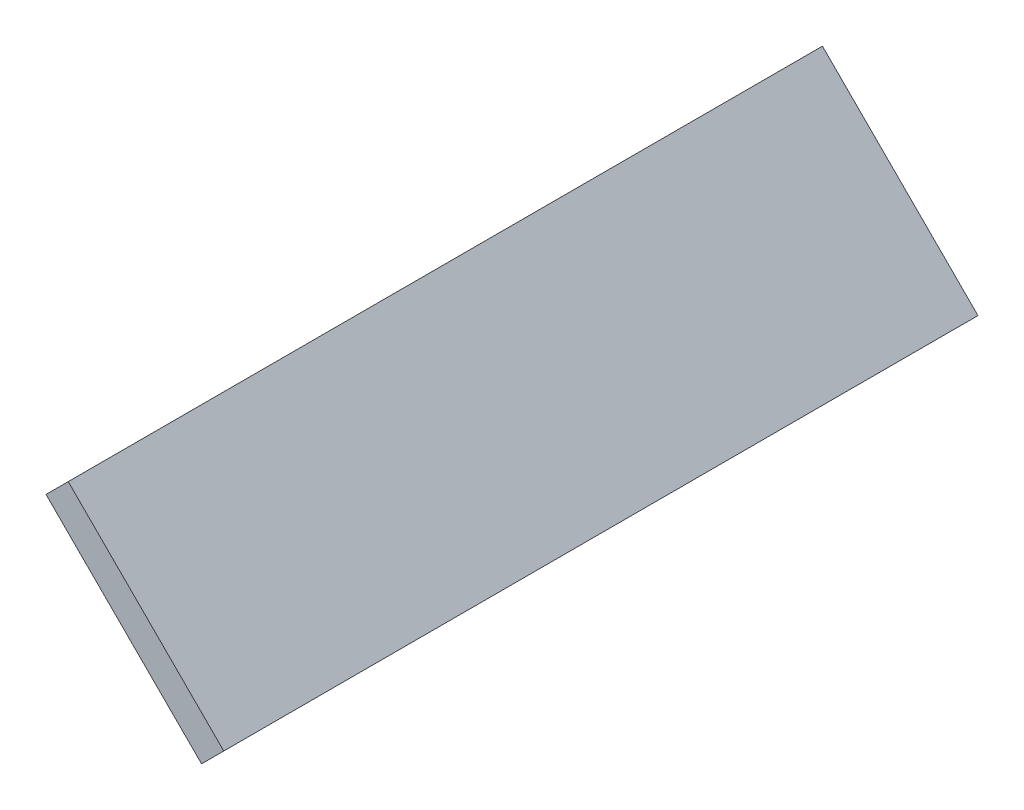
SolidWorks part; units mm, degrees
ref_plane "Front Plane" through (0, 0, 0) normal (0, 0, 1) x (1, 0, 0)
ref_plane "Top Plane" through (0, 0, 0) normal (0, 1, 0) x (1, 0, 0)
ref_plane "Right Plane" through (0, 0, 0) normal (1, 0, 0) x (0, 0, -1)
sketch "Sketch1" plane through (0, 0, 0) normal (0, 0, 1) x (1, 0, 0)
  line L0 (-105.5101, 43.1479) -> (-54.0999, -8.2622) construction
  line L1 (-20.2056, -46.6467) -> (-63.3108, -3.5414) construction
  line L2 (-58.8207, 0.9487) -> (-15.7154, -42.1565) construction
  line L3 (-71.393, 41.3598) -> (-39.9621, 9.9289)
  line L4 (-71.393, 41.3598) -> (-66.9029, 45.85)
  line L5 (-39.9621, 9.9289) -> (-35.472, 14.4191)
  line L6 (-66.9029, 45.85) -> (-35.472, 14.4191)
  line L7 (-72.2911, -22.4) -> (-103.722, 9.0309) construction
  line L8 (-76.7812, -26.8901) -> (-72.2911, -22.4) construction
extrude "Boss-Extrude1" add sketch "Sketch1" along normal up to surface (152.4 mm away)
